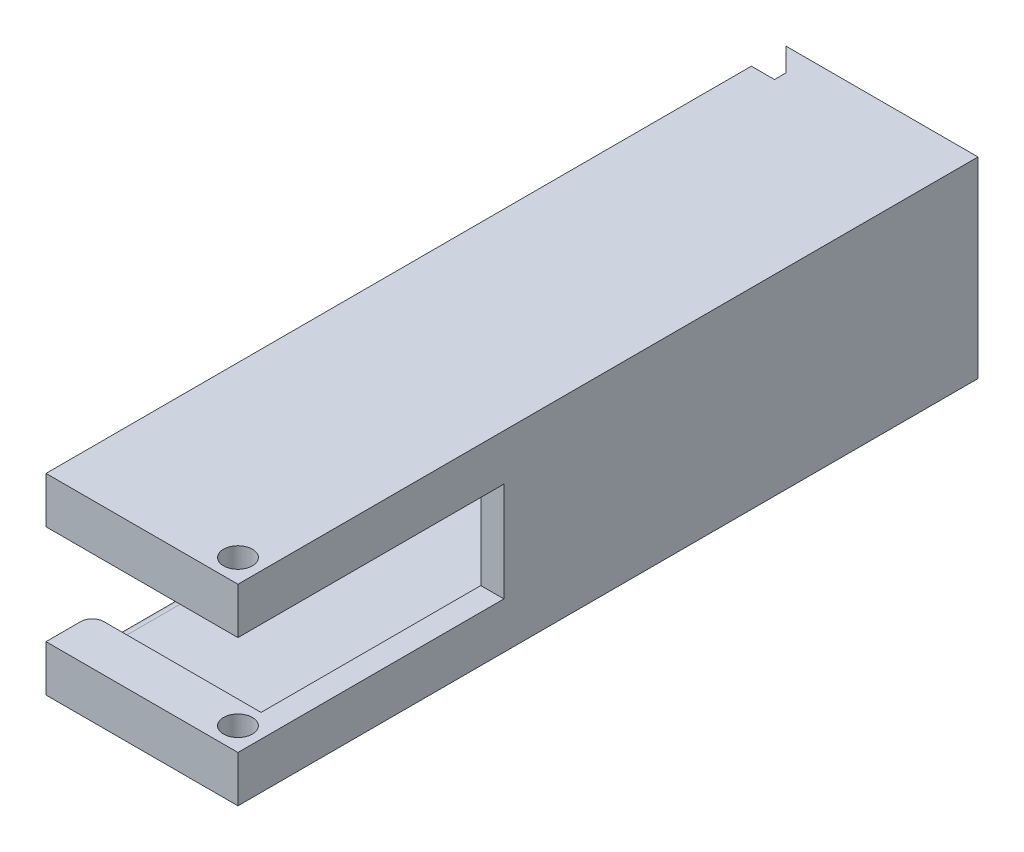
SolidWorks part; units mm, degrees
ref_plane "Front Plane" through (0, 0, 0) normal (0, 0, 1) x (1, 0, 0)
ref_plane "Top Plane" through (0, 0, 0) normal (0, 1, 0) x (1, 0, 0)
ref_plane "Right Plane" through (0, 0, 0) normal (1, 0, 0) x (0, 0, -1)
sketch "Sketch1" plane through (0, 0, 0) normal (0, 1, 0) x (1, 0, 0)
  line L1 (2, 19) -> (2, 60)
  line L2 (0, 0) -> (14.6, 0)
  line L3 (2, 60) -> (14.6, 60)
  line L5 (14.6, 0) -> (14.6, 60)
  line L7 (2, 60) -> (0, 60)
  line L8 (2, 60) -> (2, 19)
  line L9 (2, 19) -> (0, 19)
  line L10 (0, 60) -> (0, 19)
  line L11 (14.6, 60) -> (16.6, 60)
  line L12 (14.6, 60) -> (14.6, 0)
  line L14 (16.6, 60) -> (16.6, 0)
  line L19 (16.6, 0) -> (16.6, -2)
  line L20 (16.6, -2) -> (0, -2)
  line L23 (0, 19) -> (0, 0)
  line L24 (0, 0) -> (0, -2)
  dimension "D2" = 60
  dimension "D3" = 19
  dimension "D4" = 12.6
  dimension "D5" = 2
  dimension "D8" = 2
  dimension "D9" = 0
extrude "Boss-Extrude1" add sketch "Sketch1" against normal blind 2 contours L2 L24 L20 L19 L14 L11 L5 | L5 L2 | L3 L1 L9 L23 | L7 L10 L9 L1 region at (1, 0, -39.5) region at (7.9506, 0, -29.0189) region at (15.6, 0, -59.3582)
extrude "Boss-Extrude2" add sketch "Sketch1<7>" along normal blind 12.6 contours L7 L10 L9 L1 | L2 L24 L20 L19 L14 L11 L5 region at (1, 0, -39.5) region at (15.6, 0, -59.3582)
sketch "Sketch1<7>" plane through (0, 0, 0) normal (0, 1, 0) x (1, 0, 0) same geometry as "Sketch1"
sketch "Sketch2" plane through (0, 12.6, 0) normal (0, 1, 0) x (1, 0, 0)
  line L1 (0, 60) -> (16.6, 60)
  line L2 (0, 60) -> (0, -2)
  line L3 (0, -2) -> (16.6, -2)
  line L4 (16.6, 60) -> (16.6, -2)
extrude "Boss-Extrude3" add sketch "Sketch2" along normal blind 2
sketch "Sketch3" plane through (0, 0, 0) normal (-1, 0, 0) x (0, 0, 1)
  line L1 (-19, 0) -> (-60, 0)
  line L2 (-19, 0) -> (-19, 12.6)
  line L3 (-19, 12.6) -> (-60, 12.6)
  line L4 (-60, 0) -> (-60, 12.6)
  line L5 (-19, 2) -> (-60, 2)
  line L6 (-19, 2) -> (-19, 10.6)
  line L7 (-19, 10.6) -> (-60, 10.6)
  line L8 (-60, 2) -> (-60, 10.6)
  dimension "D1" = 2
  dimension "D2" = 2
extrude "Cut-Extrude1" cut sketch "Sketch3" against normal blind 2 contours L2 L7 L4 L5 region at (0, 6.3, -39.5)
sketch "Sketch4" plane through (0, 0, 0) normal (-1, 0, 0) x (0, 0, 1)
  line L0 (-19, 2) -> (-60, 2) construction
  line L2 (-19, 0) -> (-19, 0.001)
  line L3 (-59.999, 2) -> (-60, 2)
  line L4 (-60, 0) -> (-60, 2)
  line L6 (-59.999, 10.6) -> (-60, 10.6)
  line L7 (-19, 12.599) -> (-19, 12.6)
  line L9 (-60, 10.6) -> (-60, 12.6)
  line L10 (-19, 0.001) -> (-19, 2)
  line L11 (-19, 2) -> (-20.999, 2)
  line L12 (-20.999, 10.6) -> (-19, 10.6)
  line L13 (-19, 10.6) -> (-19, 12.6)
  line L14 (-60, -2) -> (-60, 2) construction
  line L15 (-58, 0) -> (-58, 0.001)
  line L16 (-19, 10.6) -> (-60, 10.6) construction
  line L20 (-58, 12.599) -> (-58, 12.6)
  line L21 (-58, 12.599) -> (-55.5654, 12.599)
  line L22 (-58, 12.599) -> (-58, 10.6)
  line L23 (-58, 10.6) -> (-55.5654, 10.6)
  line L24 (-55.5654, 12.599) -> (-55.5654, 10.6)
  line L26 (-58, 0) -> (-56, 0)
  line L27 (-58, 0) -> (-58, 2)
  line L28 (-58, 2) -> (-56, 2)
  line L29 (-56, 0) -> (-56, 2)
  line L30 (-56, 2) -> (-54, 2)
  line L31 (-56, 2) -> (-56, 0)
  line L32 (-56, 0) -> (-54, 0)
  line L33 (-54, 2) -> (-54, 0)
  line L34 (-55.5654, 12.599) -> (-53.114, 12.599)
  line L35 (-55.5654, 12.599) -> (-55.5654, 10.6)
  line L36 (-55.5654, 10.6) -> (-53.114, 10.6)
  line L37 (-53.114, 12.599) -> (-53.114, 10.6)
  arc A0 (-19, 12.599) -> (-20.999, 10.6) centre (-20.999, 12.599) cw
  arc A1 (-20.999, 2) -> (-19, 0.001) centre (-20.999, 0.001) cw
  arc A2 (-59.999, 2) -> (-58, 0.001) centre (-59.999, 0.001) cw
  arc A3 (-58, 12.599) -> (-59.999, 10.6) centre (-59.999, 12.599) cw
  point P16 (-19, 10.6)
  point P26 (-60, 1)
  line M9 (-19, 0) -> (-19, 2)
  line M10 (-19, 2) -> (-60, 2)
  line M16 (-60, 10.6) -> (-19, 10.6)
  line M17 (-19, 10.6) -> (-19, 12.6)
  dimension "D1" = 1.999
  dimension "D3" = 1.999
  dimension "D5" = 1.999
  dimension "D2" = 2
  dimension "D4" = 2
  dimension "D6" = 2
  dimension "D7" = 2
extrude "Cut-Extrude2" cut sketch "Sketch4" against normal blind 2 contours A1 M10 M9 | A0 M17 M16 region at (0, 1.5535, -19.4465) region at (0, 11.0465, -19.4465)
sketch "Sketch5" plane through (14.6, 0, 0) normal (-1, 0, 0) x (0, 0, 1)
  line L0 (0, 12.6) -> (-60, 12.6) construction
  line L1 (0, 0) -> (-19, 0)
  line L2 (0, 0) -> (0, 12.6)
  line L3 (0, 12.6) -> (-19, 12.6)
  line L4 (-19, 0) -> (-19, 12.6)
  line L5 (0, 0) -> (-60, 0) construction
  line L6 (0, 2) -> (-19, 2)
  line L7 (0, 2) -> (0, 10.6)
  line L8 (0, 10.6) -> (-19, 10.6)
  line L9 (-19, 2) -> (-19, 10.6)
  line L11 (0, 0) -> (2, 0)
  line L12 (0, 0) -> (0, 2)
  line L13 (0, 2) -> (2, 2)
  line L14 (2, 0) -> (2, 2)
  line L15 (2, 2) -> (0, 2)
  line L16 (2, 2) -> (2, 10.6)
  line L17 (2, 10.6) -> (0, 10.6)
  line L18 (0, 2) -> (0, 10.6)
  line L19 (2, 10.6) -> (0, 10.6)
  line L20 (2, 10.6) -> (2, 12.6)
  line L21 (2, 12.6) -> (0, 12.6)
  line L22 (0, 10.6) -> (0, 12.6)
  dimension "D1" = 2
  dimension "D2" = 2
  dimension "D3" = 2
extrude "Cut-Extrude4" cut sketch "Sketch5" against normal blind 14.5 and the other way blind 17.5 contours L2 L8 L4 L6 | L16 L17 L2 L13 region at (14.6, 6.3, -9.5) region at (14.6, 6.3, 1)
sketch "Sketch7" plane through (0, 0, 2) normal (0, 0, 1) x (1, 0, 0)
  line L1 (16.6, -2) -> (0, -2)
  line L2 (16.6, -2) -> (16.6, 2)
  line L3 (16.6, 2) -> (0, 2)
  line L4 (0, -2) -> (0, 2)
  line L5 (0, 10.6) -> (16.6, 10.6)
  line L6 (0, 10.6) -> (0, 14.6)
  line L7 (0, 14.6) -> (16.6, 14.6)
  line L8 (16.6, 10.6) -> (16.6, 14.6)
extrude "Boss-Extrude4" add sketch "Sketch7" along normal blind 2
sketch "Sketch9" plane through (0, 14.6, 0) normal (0, 1, 0) x (1, 0, 0)
  line L1 (16.6, -4) -> (0, -4)
  line L2 (16.6, -4) -> (16.6, 0)
  line L3 (16.6, 0) -> (0, 0)
  line L4 (0, -4) -> (0, 0)
  circle A0 centre (14.6, -2) radius 1.25
  dimension "D1" = 2
  dimension "D2" = 2
extrude "Cut-Extrude6" cut sketch "Sketch9" against normal blind 20 contours A0
fillet "Fillet3" radius 1 4 edges at (0, 12.6, -9.5) (0, 11.6, 0) (0, 1, 0) (0, 0, -9.5)
sketch "Sketch10" plane through (0, 0, -60) normal (0, 0, -1) x (-1, 0, 0)
  line L1 (0, 14.6) -> (-16.6, 14.6)
  line L2 (0, 14.6) -> (0, -2)
  line L3 (0, -2) -> (-16.6, -2)
  line L4 (-16.6, 14.6) -> (-16.6, -2)
sketch "Sketch11" plane through (0, 0, 0) normal (-1, 0, 0) x (0, 0, 1)
  line L0 (-60, 14.6) -> (4, 14.6) construction
  line L1 (1, 13.6) -> (-19, 13.6)
  line L2 (1, 13.6) -> (1, 14.6)
  line L3 (1, 14.6) -> (-19, 14.6)
  line L4 (-19, 13.6) -> (-19, 14.6)
sketch "Sketch12" plane through (0, -2, 0) normal (0, -1, 0) x (-1, 0, 0)
  line L0 (0, 60) -> (0, 59.999)
  line L1 (0, 60) -> (-2, 60)
  line L2 (0, 60) -> (0, 57)
  line L3 (0, 57) -> (-2, 57)
  line L4 (-2, 60) -> (-2, 57)
  line L5 (-1.999, 58) -> (-2, 58)
  line L6 (0, 58) -> (0, 57.999)
  line L8 (-2, 58) -> (-2, 57.999)
  line L9 (0, 57.999) -> (0, 57)
  line L10 (0, 60) -> (-2, 57.999)
  line M14 (0, -4) -> (0, 60)
  dimension "D1" = 3
  dimension "D2" = 2
extrude "Cut-Extrude7" cut sketch "Sketch12" against normal blind 21 contours L10 L4 L3 L2 M14 region at (0.8332, -2, -58.0832)
sketch "Sketch13" plane through (0, 0, -60) normal (0, 0, -1) x (-1, 0, 0)
  line L0 (0, 10.6) -> (0, 14.6) construction
  line L1 (-2, 10.6) -> (0, 10.6)
  line L2 (-2, 10.6) -> (-2, 12.6)
  line L3 (-2, 12.6) -> (0, 12.6)
  line L4 (0, 10.6) -> (0, 12.6)
  line L6 (-2, 2) -> (0, 2)
  line L7 (-2, 2) -> (-2, 0)
  line L8 (-2, 0) -> (0, 0)
  line L9 (0, 2) -> (0, 0)
extrude "Cut-Extrude8" cut sketch "Sketch13" against normal blind 3
